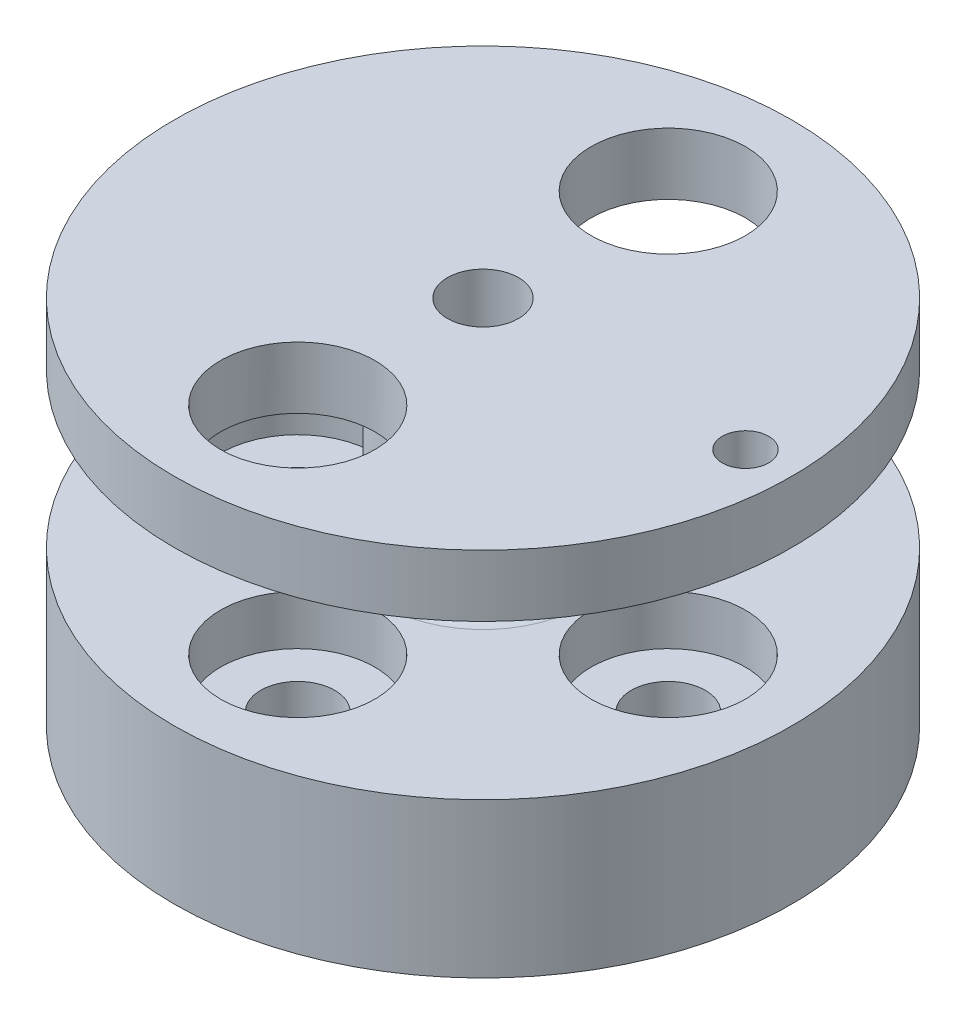
SolidWorks part; units mm, degrees
ref_plane "Front Plane" through (0, 0, 0) normal (0, 0, 1) x (1, 0, 0)
ref_plane "Top Plane" through (0, 0, 0) normal (0, 1, 0) x (1, 0, 0)
ref_plane "Right Plane" through (0, 0, 0) normal (1, 0, 0) x (0, 0, -1)
sketch "Sketch1" plane through (0, 0, 0) normal (0, 1, 0) x (1, 0, 0)
  circle A0 centre (0, 0) radius 10
  dimension "D1" = 20
extrude "bottom" add sketch "Sketch1" along normal blind 5
sketch "Sketch2" plane through (0, 5, 0) normal (0, 1, 0) x (1, 0, 0)
  circle A0 centre (6, 0) radius 1.2
  point P0 (6, 0)
  dimension "D1" = 2.4
  dimension "D2" = 6
hole_wizard "CBORE for M2 Pan Head Screw1" positions "Sketch2" profile "Sketch3" counterbore size "M2" standard "DIN" end condition through all
sketch "Sketch3" plane through (6, 5, 0) normal (1, 0, 0) x (0, 0, 1)
  line L0 (0, 0) -> (0, 5)
  line L1 (0, 5) -> (1.2, 5)
  line L3 (1.2, 5) -> (1.2, 1.6)
  line L4 (1.2, 1.6) -> (2.5, 1.6)
  line L5 (2.5, 1.6) -> (2.5, 0)
  line L7 (2.5, 0) -> (0, 0)
  line L11 (0, -6.35) -> (0, 107.95) construction
  dimension "Thru Hole Dia." = 2.4
  dimension "Thru Hole Depth" = 5
  dimension "C'Bore Dia." = 5
  dimension "C'Bore Depth" = 1.6
sketch "Sketch4" plane through (0, 5, 0) normal (0, 1, 0) x (1, 0, 0)
  circle A0 centre (0, 0) radius 2.75
  dimension "D1" = 5.5
extrude "groove" add sketch "Sketch4" along normal blind 5
pattern_circular "CirPattern1" count 4 over 360 about axis through (0, 5, 0) along (0, 1, 0) of "CBORE for M2 Pan Head Screw1"
sketch "Sketch7" plane through (0, 10, 0) normal (0, 1, 0) x (1, 0, 0)
  circle A0 centre (0, 0) radius 10 construction
  circle A1 centre (0, 0) radius 10
extrude "top" add sketch "Sketch7" along normal blind 2
sketch "Sketch8" plane through (0, 12, 0) normal (0, 1, 0) x (1, 0, 0)
  circle A0 centre (8.5, 0) radius 0.75
  circle A1 centre (0, 0) radius 10 construction
  dimension "D1" = 1.5
  dimension "D2" = 8.5
extrude "thread_terminal" cut sketch "Sketch8" against normal up to surface (2 mm away) up to face at (0, 10, 2.75)
sketch "Sketch9" plane through (0, 5, 0) normal (0, 1, 0) x (1, 0, 0)
  circle A0 centre (0, 0) radius 1.15
  dimension "D1" = 2.3
extrude "M2 pin_insert" cut sketch "Sketch9" along normal up to surface (7 mm away) up to face at (8.5, 12, 0.75)
fillet "Fillet1" radius 0.5 1 edges at (0, 5, 2.75)
split "Split1" bodies to split 108 resulting bodies 109 110 split by face at (8.5, 10, 0.75)
sketch "Sketch10" plane through (0, 12, 0) normal (0, 1, 0) x (1, 0, 0)
  circle A0 centre (0, -6) radius 2.5 construction
  circle A1 centre (0, -6) radius 2.5
extrude "Cut-Extrude1" cut sketch "Sketch10" against normal up to surface (2 mm away) up to face at (0, 10, -1.15)
pattern_circular "holes_for_screwdrivers" count 2 over 360 about axis through (0, 12, 0) along (0, 1, 0) of "Cut-Extrude1"
